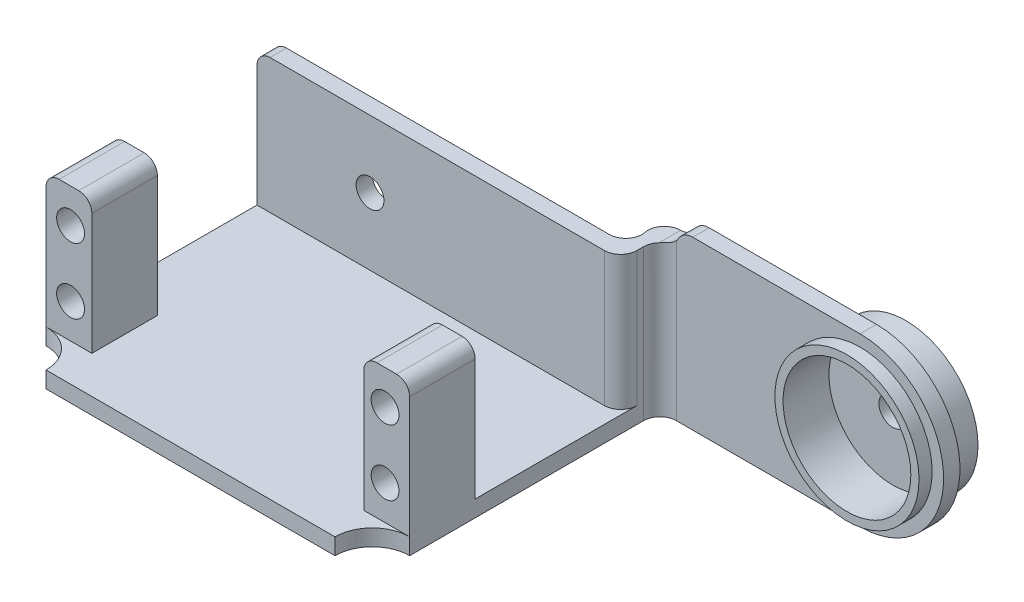
SolidWorks part; units mm, degrees
ref_plane "Front" through (0, 0, 0) normal (0, 0, 1) x (1, 0, 0)
ref_plane "Top" through (0, 0, 0) normal (0, 1, 0) x (1, 0, 0)
ref_plane "Right" through (0, 0, 0) normal (1, 0, 0) x (0, 0, -1)
sketch "Sketch1" plane through (0, 0, 0) normal (0, 1, 0) x (1, 0, 0)
  line L1 (0, 0) -> (55.5, 0)
  line L2 (0, 0) -> (0, 37.9)
  line L3 (0, 37.9) -> (55.5, 37.9)
  line L4 (55.5, 0) -> (55.5, 37.9)
  dimension "D1" = 37.9
  dimension "D2" = 55.5
extrude "bracketBase" add sketch "Sketch1" along normal blind 2.5
ref_plane "referencePlane1" through (0, 0, -8.2) normal (0, 0, 1) x (1, 0, 0)
sketch "Sketch2" plane through (0, 0, -8.2) normal (0, 0, 1) x (1, 0, 0)
  line L0 (27.75, 2.5) -> (27.75, 23) construction
  line L1 (0, 2.5) -> (7, 2.5)
  line L2 (0, 2.5) -> (0, 23)
  line L3 (0, 23) -> (7, 23)
  line L4 (7, 2.5) -> (7, 23)
  line L5 (0, 2.5) -> (55.5, 2.5) construction
  line L6 (55.5, 23) -> (48.5, 23)
  line L7 (48.5, 2.5) -> (48.5, 23)
  line L8 (55.5, 2.5) -> (48.5, 2.5)
  line L9 (55.5, 2.5) -> (55.5, 23)
  dimension "D1" = 20.5
  dimension "D2" = 7
extrude "servoMountingHoleTabs" add sketch "Sketch2" along normal blind 2.5
sketch "Sketch3" plane through (0, 0, -5.7) normal (0, 0, 1) x (1, 0, 0)
  line L0 (0, 12.75) -> (7, 12.75) construction
  line L3 (0, 23) -> (0, 2.5) construction
  line L4 (7, 2.5) -> (7, 23) construction
  line L5 (7, 23) -> (0, 23) construction
  line L6 (27.75, 2.5) -> (27.75, 23) construction
  line L7 (0, 2.5) -> (55.5, 2.5) construction
  circle A0 centre (3.75, 17.75) radius 2.125
  circle A1 centre (3.75, 7.75) radius 2.125
  circle A2 centre (51.75, 7.75) radius 2.125
  circle A3 centre (51.75, 17.75) radius 2.125
  dimension "D1" = 4.25
  dimension "D2" = 3.75
  dimension "D3" = 5.25
extrude "servoMountingHoles" cut sketch "Sketch3" against normal blind 2.5
sketch "Sketch4" plane through (0, 0, 0) normal (0, 1, 0) x (1, 0, 0)
  line L0 (55.5, 8.2) -> (55.5, 37.9) construction
  line L1 (0, 37.9) -> (55.5, 37.9)
  line L2 (0, 37.9) -> (0, 40.4)
  line L3 (0, 40.4) -> (55.5, 40.4)
  line L4 (55.5, 37.9) -> (55.5, 40.4)
  dimension "D1" = 2.5
extrude "baseWall" add sketch "Sketch4" along normal up to surface (23 mm away) up to face at (3.5, 23, -6.95)
sketch "Sketch6" plane through (0, 2.5, 0) normal (0, 1, 0) x (1, 0, 0)
  circle A0 centre (0, 0) radius 5.7
  circle A1 centre (55.5, 0) radius 5.7
extrude "baseTrim" cut sketch "Sketch6" against normal blind 2.5
fillet "Fillet1" radius 2 6 edges at (7, 23, -6.95) (48.5, 23, -6.95) (0, 23, -6.95) (55.5, 23, -6.95) (55.5, 23, -39.15) (0, 23, -39.15)
sketch "Sketch7" plane through (0, 0, -40.4) normal (0, 0, -1) x (-1, 0, 0)
  line L0 (0, 21) -> (0, 0) construction
  line L1 (-55.5, 0) -> (0, 0) construction
  circle A0 centre (-17.25, 12.75) radius 2.125
  dimension "D1" = 4.25
  dimension "D2" = 17.25
  dimension "D3" = 12.75
extrude "M4mountingHole" cut sketch "Sketch7" against normal blind 10
sketch "Sketch8" plane through (0, 0, -8.2) normal (0, 0, -1) x (-1, 0, 0)
  line L4 (-48.5, 2.5) -> (-48.5, 21)
  line L5 (-50.5, 23) -> (-53.5, 23)
  line L6 (-55.5, 21) -> (-55.5, 2.5)
  line L7 (-55.5, 2.5) -> (-48.5, 2.5)
  line L8 (-48.5, 2.5) -> (-48.5, 21)
  line L9 (-50.5, 23) -> (-53.5, 23)
  line L10 (-55.5, 21) -> (-55.5, 2.5)
  line L11 (-55.5, 2.5) -> (-48.5, 2.5)
  line L12 (-2, 23) -> (-5, 23)
  line L13 (-7, 21) -> (-7, 2.5)
  line L14 (-7, 2.5) -> (0, 2.5)
  line L15 (0, 2.5) -> (0, 21)
  line L16 (-2, 23) -> (-5, 23)
  line L17 (-7, 21) -> (-7, 2.5)
  line L18 (-7, 2.5) -> (0, 2.5)
  line L19 (0, 2.5) -> (0, 21)
  circle A0 centre (-51.75, 17.75) radius 2.125 construction
  circle A1 centre (-51.75, 17.75) radius 2.125
  arc A2 (-48.5, 21) -> (-50.5, 23) centre (-50.5, 21) ccw
  arc A3 (-53.5, 23) -> (-55.5, 21) centre (-53.5, 21) ccw
  arc A4 (-48.5, 21) -> (-50.5, 23) centre (-50.5, 21) ccw
  arc A5 (-53.5, 23) -> (-55.5, 21) centre (-53.5, 21) ccw
  arc A6 (-5, 23) -> (-7, 21) centre (-5, 21) ccw
  arc A7 (0, 21) -> (-2, 23) centre (-2, 21) ccw
  arc A8 (-5, 23) -> (-7, 21) centre (-5, 21) ccw
  arc A9 (0, 21) -> (-2, 23) centre (-2, 21) ccw
  circle A10 centre (-51.75, 7.75) radius 2.125 construction
  circle A11 centre (-51.75, 7.75) radius 2.125
  circle A12 centre (-3.75, 17.75) radius 2.125 construction
  circle A13 centre (-3.75, 17.75) radius 2.125
  circle A14 centre (-3.75, 7.75) radius 2.125 construction
  circle A15 centre (-3.75, 7.75) radius 2.125
  dimension "D1" = 0
  dimension "D2" = 0
extrude "tabExtension" add sketch "Sketch8" along normal blind 7.5
sketch "Sketch10" plane through (0, 0, 0) normal (0, -1, 0) x (1, 0, 0)
  line L0 (101.5796, -43.8997) -> (55.5, -43.8997)
  line L1 (101.5796, -46.3997) -> (47.5, -46.3997)
  line L2 (101.5796, -43.8997) -> (101.5796, -46.3997)
  line L3 (2, -40.4) -> (53.5, -40.4) construction
  line L4 (55.5, -40.4) -> (55.5, -37.9)
  line L5 (55.5, -43.8997) -> (55.5, -40.4)
  line L7 (47.5, -40.4) -> (47.5, -46.3997)
  line L8 (55.5, -5.7) -> (55.5, -40.4) construction
  line L9 (55.5, -37.9) -> (47.5, -37.9)
  line L10 (47.5, -37.9) -> (47.5, -40.4)
  line L11 (55.5, -37.9) -> (0, -37.9) construction
  dimension "D1" = 46.0796
  dimension "D2" = 54.0796
  dimension "D3" = 2.5
  dimension "D4" = 3.4997
extrude "Boss-Extrude1" add sketch "Sketch10" against normal blind 25.5
ref_plane "Plane1" through (0, 0, -41.8997) normal (0, 0, 1) x (1, 0, 0)
sketch "Sketch12" plane through (0, 0, -41.8997) normal (0, 0, 1) x (1, 0, 0)
  line L0 (55.5, 2.5) -> (55.5, 21) construction
  circle A0 centre (86.0398, 12.75) radius 11
  dimension "D1" = 22
  dimension "D2" = 12.75
  dimension "D3" = 30.5398
extrude "Boss-Extrude2" add sketch "Sketch12" against normal blind 9
sketch "Sketch13" plane through (0, 0, -41.8997) normal (0, 0, 1) x (1, 0, 0)
  circle A0 centre (86.0398, 12.75) radius 9.75
  dimension "D1" = 19.5
extrude "Cut-Extrude1" cut sketch "Sketch13" against normal offset from surface (7 mm away) 2 up to face at (97.0398, 12.75, -50.8997)
sketch "Sketch14" plane through (0, 0, -48.8997) normal (0, 0, 1) x (1, 0, 0)
  circle A0 centre (86.0398, 12.75) radius 2.125
  dimension "D1" = 4.25
extrude "Cut-Extrude2" cut sketch "Sketch14" against normal blind 2
sketch "Sketch15" plane through (47.5, 0, 0) normal (-1, 0, 0) x (0, 0, 1)
  line L0 (-46.3997, 25.5) -> (-46.3997, 0) construction
  line L1 (-37.9, 25.5) -> (-46.3997, 25.5)
  line L2 (-37.9, 25.5) -> (-37.9, 23)
  line L3 (-37.9, 23) -> (-46.3997, 23)
  line L4 (-46.3997, 25.5) -> (-46.3997, 23)
  line L5 (-37.9, 23) -> (-40.4, 23) construction
extrude "Cut-Extrude3" cut sketch "Sketch15" against normal up to surface (8 mm away) up to face at (55.5, 11.1667, -23.5666)
fillet "Fillet2" radius 2.5 2 edges at (47.5, 11.5, -46.3997) (55.5, 12.75, -37.9)
fillet "Fillet4" radius 2.5 2 edges at (55.5, 11.5, -43.8997) (47.5, 11.5, -40.4)
sketch "Sketch16" plane through (0, 0, -43.8997) normal (0, 0, 1) x (1, 0, 0)
  line L0 (101.5796, 25.5) -> (55.5, 25.5) construction
  line L1 (60.5, 25.5) -> (55.5, 25.5)
  line L2 (55.5, 25.5) -> (55.5, 23)
  line L3 (55.5, 23) -> (58, 23)
  arc A0 (58, 23) -> (60.5, 25.5) centre (60.5, 23) cw
extrude "Cut-Extrude4" cut sketch "Sketch16" against normal through all
fillet "Fillet5" radius 2.5 1 edges at (58, 23, -45.1497)
sketch "Sketch17" plane through (0, 0, -43.8997) normal (0, 0, 1) x (1, 0, 0)
  line L0 (86.0398, 0) -> (101.5796, 0)
  line L1 (101.5796, 0) -> (101.5796, 25.5)
  line L2 (101.5796, 25.5) -> (86.0398, 25.5)
  arc A0 (86.0398, 0) -> (86.0398, 25.5) centre (86.0398, 12.75) ccw
extrude "Cut-Extrude5" cut sketch "Sketch17" against normal blind 25
sketch "Sketch18" plane through (0, 23, 0) normal (0, 1, 0) x (1, 0, 0)
  line L0 (45, 40.4) -> (51.2708, 40.4)
  line L1 (56.1699, 46.3997) -> (50, 46.3997) construction
  line L2 (47.5, 43.8997) -> (47.5, 42.9) construction
  line L3 (47.5, 43.8997) -> (47.5, 42.9)
  line L4 (56.1699, 46.3997) -> (50, 46.3997)
  arc A0 (56.1699, 46.3997) -> (53.7204, 43.3998) centre (56.1699, 43.8997) ccw
  arc A1 (53.7204, 43.3998) -> (51.2708, 40.4) centre (51.2708, 42.9) cw
  arc A2 (45, 40.4) -> (47.5, 42.9) centre (45, 42.9) ccw construction
  arc A3 (45, 40.4) -> (47.5, 42.9) centre (45, 42.9) ccw
  arc A4 (50, 46.3997) -> (47.5, 43.8997) centre (50, 43.8997) ccw construction
  arc A5 (50, 46.3997) -> (47.5, 43.8997) centre (50, 43.8997) ccw
  dimension "D1" = 2.5
  dimension "D2" = 2.5
extrude "Cut-Extrude6" cut sketch "Sketch18" against normal through all
ref_plane "Plane2" through (0, 0, 0) normal (0, 0, 1) x (1, 0, 0)
mirror "Mirror1" about plane through (0, 0, 0) normal (0, 0, 1) of bodies 118
sketch "Sketch19" plane through (0, 0, 0) normal (0, 0, 1) x (1, 0, 0)
  line L1 (-73.8417, 72.2477) -> (103.3977, 72.2477)
  line L2 (-73.8417, 72.2477) -> (-73.8417, -56.9909)
  line L3 (-73.8417, -56.9909) -> (103.3977, -56.9909)
  line L4 (103.3977, 72.2477) -> (103.3977, -56.9909)
extrude "Cut-Extrude7" cut sketch "Sketch19" along normal blind 81
